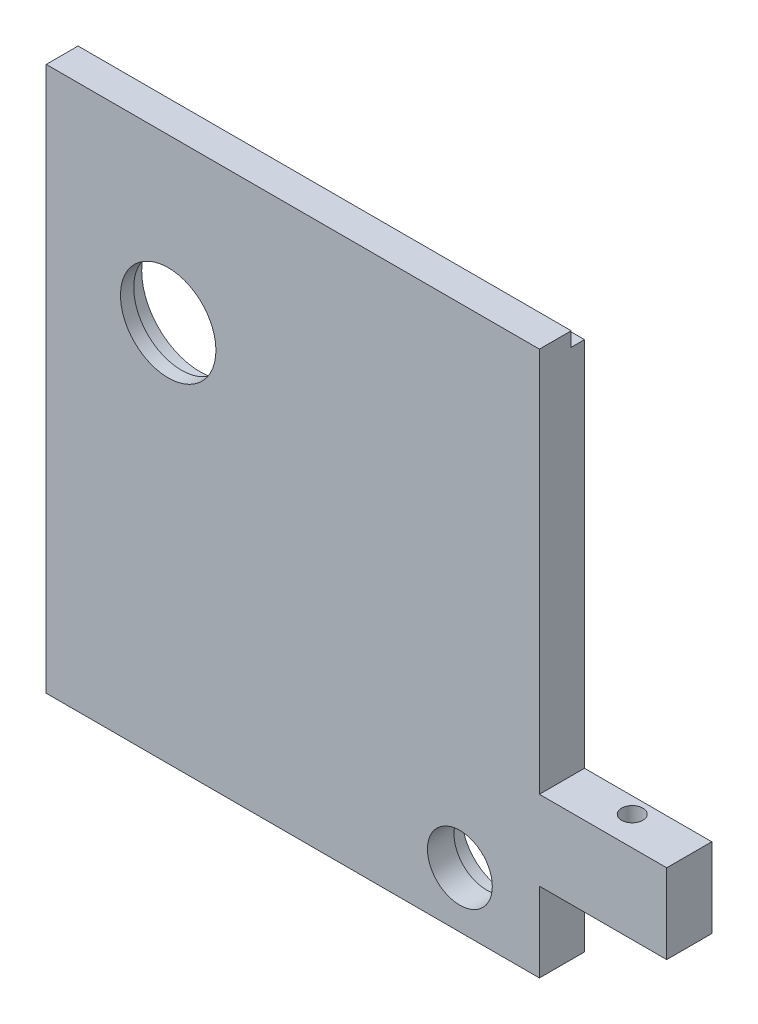
SolidWorks part; units mm, degrees
ref_plane "Front Plane" through (0, 0, 0) normal (0, 0, 1) x (1, 0, 0)
ref_plane "Top Plane" through (0, 0, 0) normal (0, 1, 0) x (1, 0, 0)
ref_plane "Right Plane" through (0, 0, 0) normal (1, 0, 0) x (0, 0, -1)
sketch "Sketch1" plane through (0, 0, 0) normal (0, 0, 1) x (1, 0, 0)
  line L1 (-76.1871, 67.6281) -> (16.8129, 67.6281)
  line L2 (-76.1871, 67.6281) -> (-76.1871, -35.0719)
  line L3 (-76.1871, -35.0719) -> (16.8129, -35.0719)
  line L4 (16.8129, 67.6281) -> (16.8129, -35.0719)
  dimension "D1" = 93
  dimension "D2" = 102.7
extrude "Boss-Extrude2" add sketch "Sketch1" along normal blind 6 contours L1 L4 L3 L2
sketch "Sketch3" plane through (0, 0, 0) normal (0, 0, -1) x (-1, 0, 0)
  line L0 (76.1871, -35.0719) -> (-16.8129, -35.0719) construction
  line L1 (-16.8129, 64.9281) -> (18.1871, 64.9281)
  line L2 (-16.8129, 64.9281) -> (-16.8129, -35.0719)
  line L3 (-16.8129, -35.0719) -> (18.1871, -35.0719)
  line L4 (18.1871, 64.9281) -> (18.1871, -35.0719)
  line L5 (-16.8129, 67.6281) -> (-16.8129, -35.0719) construction
  dimension "D1" = 0
  dimension "D2" = 0
  dimension "D3" = 35
  dimension "D4" = 100
extrude "Boss-Extrude3" add sketch "Sketch3" along normal blind 2.5
sketch "Sketch4" plane through (16.8129, 0, 0) normal (1, 0, 0) x (0, 0, -1)
  line L0 (-6, 67.6281) -> (-6, -35.0719) construction
  line L1 (-6, -5.0719) -> (2.5, -5.0719)
  line L2 (-6, -5.0719) -> (-6, -20.0719)
  line L3 (-6, -20.0719) -> (2.5, -20.0719)
  line L4 (2.5, -5.0719) -> (2.5, -20.0719)
  line L5 (2.5, 64.9281) -> (2.5, -35.0719) construction
  line L6 (-6, -35.0719) -> (2.5, -35.0719) construction
  dimension "D1" = 15
  dimension "D2" = 15
extrude "Boss-Extrude4" add sketch "Sketch4" along normal blind 24
sketch "Sketch5" plane through (0, -5.0719, 0) normal (0, 1, 0) x (1, 0, 0)
  line L0 (40.8129, -6) -> (16.8129, -6) construction
  line L2 (16.8129, 2.5) -> (16.8129, -6) construction
  circle A0 centre (28.8129, -0.5) radius 2
  dimension "D2" = 4
  dimension "D3" = 12
  dimension "D1" = 5.5
extrude "Cut-Extrude1" cut sketch "Sketch5" against normal blind 50
sketch "Sketch6" plane through (0, 0, -2.5) normal (0, 0, -1) x (-1, 0, 0)
  line L0 (-16.8129, -35.0719) -> (18.1871, -35.0719) construction
  line L1 (-16.8129, -20.0719) -> (-16.8129, -35.0719) construction
  circle A0 centre (-1.8129, -24.5719) radius 8.115
  dimension "D1" = 16.23
  dimension "D2" = 10.5
  dimension "D3" = 15
extrude "Cut-Extrude2" cut sketch "Sketch6" against normal blind 50
sketch "Sketch7" plane through (0, 0, 0) normal (0, 0, -1) x (-1, 0, 0)
  line L0 (76.1871, -35.0719) -> (18.1871, -35.0719) construction
  line L2 (-16.8129, 64.9281) -> (-16.8129, -5.0719) construction
  circle A0 centre (53.1871, 36.9281) radius 11
  dimension "D1" = 22
  dimension "D2" = 72
  dimension "D3" = 70
extrude "Cut-Extrude3" cut sketch "Sketch7" against normal blind 50
extrude "Extrude-Thin1" add sketch "Sketch7" along normal blind 2.5 from surface thin starting at face at (-42.1871, 36.9281, 6) thin type one direction reverse wall 2
extrude "Extrude-Thin2" add sketch "Sketch6<2>" along normal blind 5 from surface thin starting at face at (9.9279, -24.5719, 6) thin type one direction reverse wall 2
sketch "Sketch6<2>" plane through (0, 0, -2.5) normal (0, 0, -1) x (-1, 0, 0) same geometry as "Sketch6"
